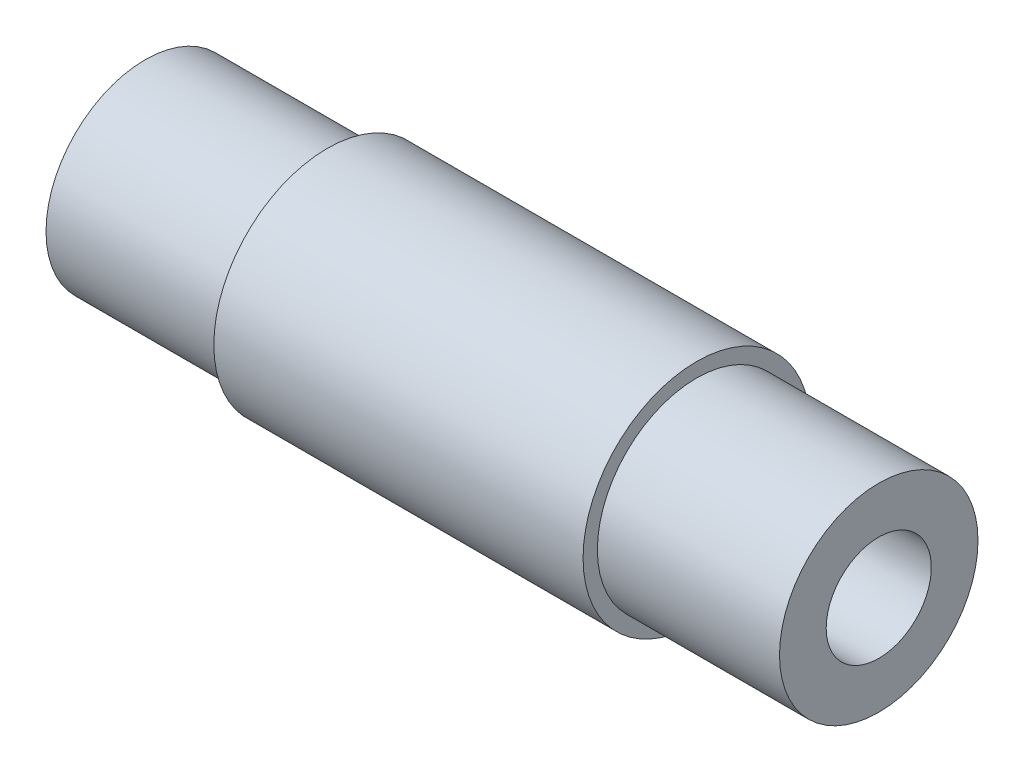
SolidWorks part; units mm, degrees
ref_plane "Front Plane" through (0, 0, 0) normal (0, 0, 1) x (1, 0, 0)
ref_plane "Top Plane" through (0, 0, 0) normal (0, 1, 0) x (1, 0, 0)
ref_plane "Right Plane" through (0, 0, 0) normal (1, 0, 0) x (0, 0, -1)
sketch "Filter_F1 Sketch" plane through (0, 0, 0) normal (0, 0, 1) x (1, 0, 0)
  line L0 (-1000, 0) -> (1000, 0) construction
  line L1 (-44.3, 0) -> (-44.3, 11.988)
  line L2 (-44.3, 11.988) -> (-22.3, 11.988)
  line L3 (-22.3, 11.988) -> (-22.3, 13.716)
  line L4 (-22.3, 13.716) -> (22.3, 13.716)
  line L5 (22.3, 13.716) -> (22.3, 11.988)
  line L6 (22.3, 11.988) -> (44.3, 11.988)
  line L7 (44.3, 11.988) -> (44.3, 0)
  line L8 (44.3, 0) -> (-44.3, 0)
revolve "Filter_F1" add sketch "Filter_F1 Sketch" angle 360 about L0
ref_axis "Engine Axis" through (48.73, 0, 0) along (-1, 0, 0)
sketch "Socket 1 Sketch" plane through (0, 0, 0) normal (0, 0, 1) x (1, 0, 0)
  line L0 (-1000, 0) -> (1000, 0) construction
  line L1 (-45.3, 0) -> (-45.3, 6.35)
  line L2 (-45.3, 6.35) -> (-21.4, 6.35)
  line L3 (-21.4, 6.35) -> (-21.4, 0)
  line L4 (-21.4, 0) -> (-45.3, 0)
revolve "Socket 1" cut sketch "Socket 1 Sketch" angle 360 about L0
sketch "Socket 2 Sketch" plane through (0, 0, 0) normal (0, 0, 1) x (1, 0, 0)
  line L0 (-1000, 0) -> (1000, 0) construction
  line L1 (21.4, 0) -> (21.4, 6.35)
  line L2 (21.4, 6.35) -> (45.3, 6.35)
  line L3 (45.3, 6.35) -> (45.3, 0)
  line L4 (45.3, 0) -> (21.4, 0)
revolve "Socket 2" cut sketch "Socket 2 Sketch" angle 360 about L0
